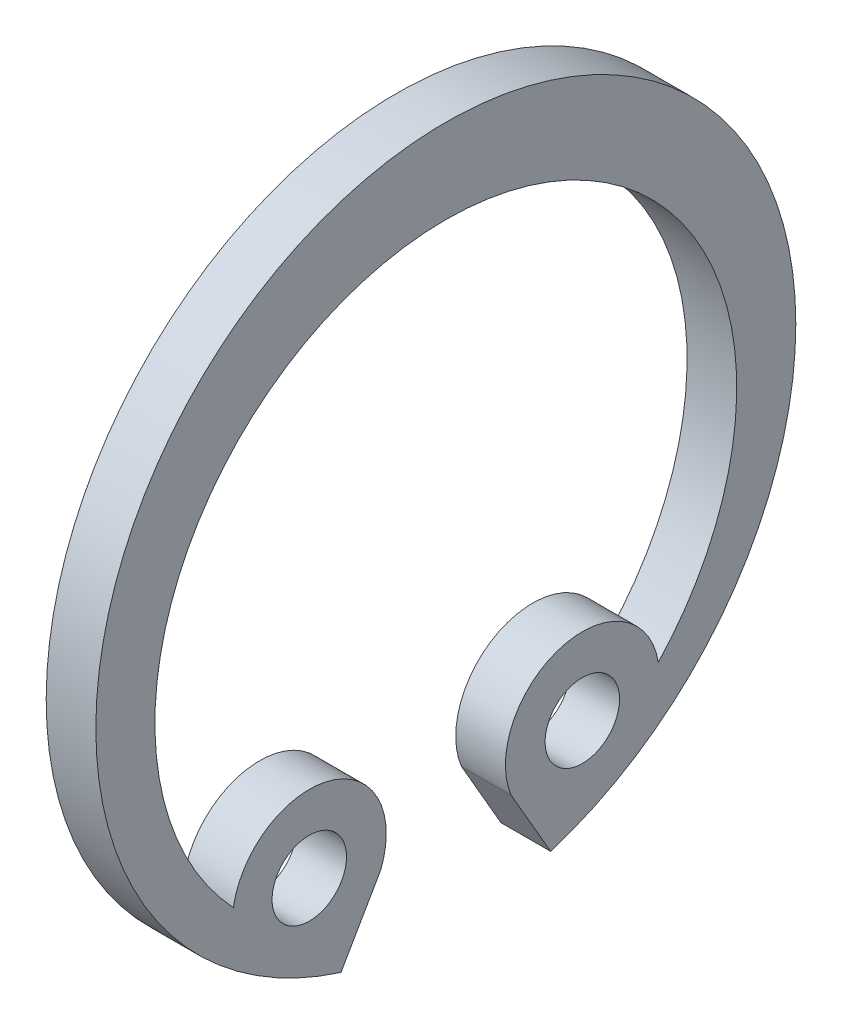
SolidWorks part; units mm, degrees
ref_plane "Front Plane" through (0, 0, 0) normal (0, 0, 1) x (1, 0, 0)
ref_plane "Top Plane" through (0, 0, 0) normal (0, 1, 0) x (1, 0, 0)
ref_plane "Right Plane" through (0, 0, 0) normal (1, 0, 0) x (0, 0, -1)
ref_plane "Plane1" through (0, 0, 0) normal (1, 0, 0) x (0, 0, -1)
sketch "Sketch1" plane through (0, 0, 0) normal (1, 0, 0) x (0, 0, -1)
  line L0 (-2.1115, -6.7264) -> (-1.3118, -5.3413)
  line L1 (1.3118, -5.3413) -> (2.1115, -6.7264)
  arc A0 (2.1115, -6.7264) -> (-2.1115, -6.7264) centre (0, 0) ccw
  arc A1 (-1.3118, -5.3413) -> (-4.2797, -4.513) centre (-2.75, -4.7631) ccw
  arc A2 (-4.2797, -4.513) -> (4.2797, -4.513) centre (0, -0.51) cw
  arc A3 (4.2797, -4.513) -> (1.3118, -5.3413) centre (2.75, -4.7631) ccw
  circle A4 centre (2.75, -4.7631) radius 0.75
  circle A5 centre (-2.75, -4.7631) radius 0.75
extrude "Boss-Extrude1" add sketch "Sketch1" against normal blind 0.5 and the other way blind 0.5
